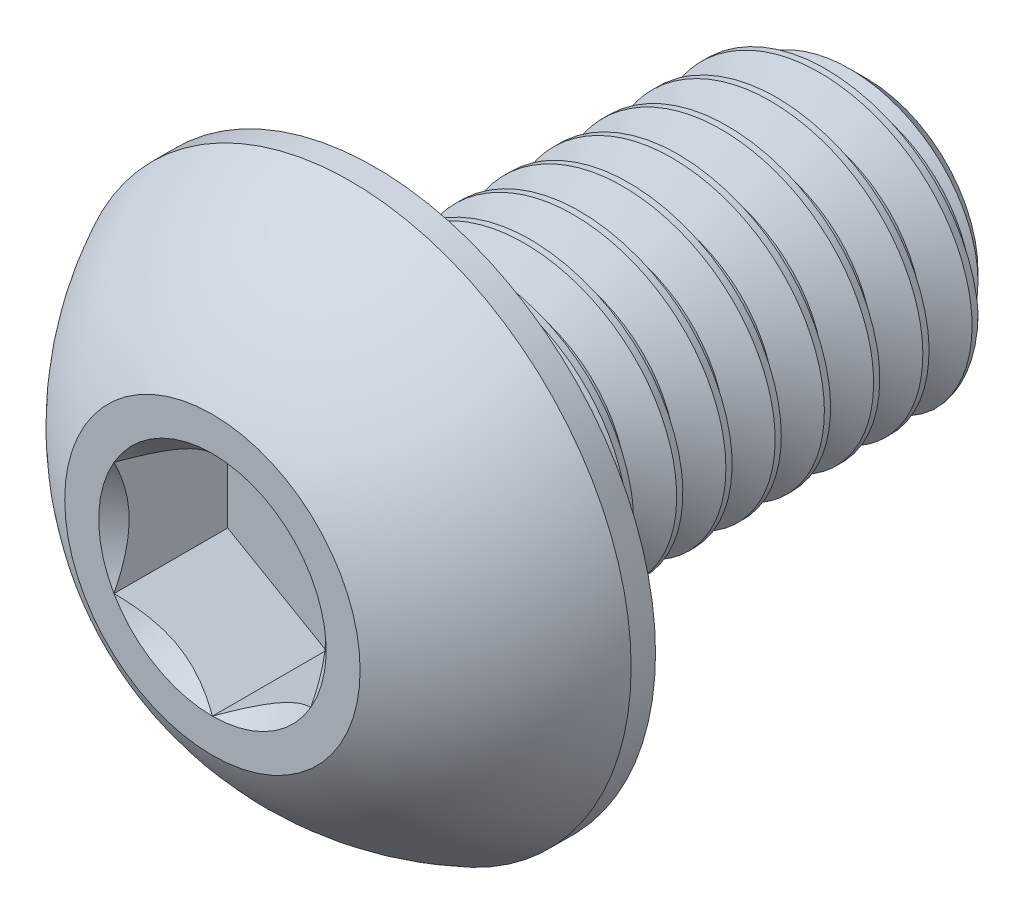
SolidWorks part; units mm, degrees
ref_plane "Front" through (0, 0, 0) normal (0, 0, 1) x (1, 0, 0)
ref_plane "Top" through (0, 0, 0) normal (0, 1, 0) x (1, 0, 0)
ref_plane "Right" through (0, 0, 0) normal (1, 0, 0) x (0, 0, -1)
sketch "Sketch1" plane through (0, 0, 0) normal (1, 0, 0) x (0, 0, -1)
  line L2 (1.65, 1.5) -> (6.65, 1.5)
  line L3 (6.65, 1.5) -> (6.65, 0)
  line L4 (6.65, 0) -> (1.65, 0)
  line L6 (1.4025, 2.85) -> (1.65, 2.85) construction
  line L7 (6.65, 1.5) -> (6.65, -1.5) construction
  line L8 (0, 0) -> (1.65, 0) construction
  line L9 (1.65, 2.85) -> (1.65, -2.85) construction
  line L11 (1.65, 1.5) -> (1.65, 0)
  line L13 (0, 1) -> (0, -1) construction
  line L14 (0, 1) -> (0, 1.5) construction
  line L15 (6.65, -1.5) -> (6.15, -1.5) construction
  arc A3 (0, 1.5) -> (1.4025, 2.85) centre (2.7948, 0) cw construction
  dimension "D1" = 0.2475
  dimension "Pitch" = 0.5
revolve "Revolve1" add sketch "Sketch1" angle 360 mid plane about L4
sketch "Sketch7" plane through (0, 0, 0) normal (1, 0, 0) x (0, 0, -1)
  line L6 (1.4025, 2.85) -> (1.65, 2.85) construction
  line L8 (0, 0) -> (1.65, 0) construction
  line L11 (1.65, 2.85) -> (1.65, -2.85) construction
  line L12 (1.4025, 2.85) -> (1.65, 2.85)
  line L13 (0, 0) -> (1.65, 0)
  line L14 (0, 1) -> (0, -1) construction
  line L15 (1.65, 2.85) -> (1.65, 0)
  line L16 (0, 1.5) -> (0, 0)
  arc A2 (1.4025, 2.85) -> (0, 1.5) centre (2.7948, 0) ccw construction
  arc A3 (1.4025, 2.85) -> (0, 1.5) centre (2.7948, 0) ccw
revolve "Revolve2" add sketch "Sketch7" angle 360 mid plane about L13
sketch "Sketch5" plane through (0, 0, 0) normal (0, 0, 1) x (1, 0, 0)
  line L1 (1, -0.5774) -> (1, 0.5774)
  line L2 (1, 0.5774) -> (0, 1.1547)
  line L3 (0, 1.1547) -> (-1, 0.5774)
  line L4 (-1, 0.5774) -> (-1, -0.5774)
  line L5 (-1, -0.5774) -> (0, -1.1547)
  line L6 (0, -1.1547) -> (1, -0.5774)
  circle A0 centre (0, 0) radius 1 construction
extrude "Cut-Extrude2" cut sketch "Sketch5" against normal blind 1.155
sketch "Sketch6" plane through (0, 0, 0) normal (0, 0, 1) x (1, 0, 0)
  circle A0 centre (0, 0) radius 1.1547
extrude "Cut-Extrude3" cut sketch "Sketch6" against normal blind 1.155 draft 45
sketch "Sketch11" plane through (0, 0, 0) normal (1, 0, 0) x (0, 0, -1)
  line L0 (1.65, -2.85) -> (1.65, 2.85)
  point P4 (1.65, 0)
split "Split1" trim tools "Sketch11" bodies to split 113 resulting bodies 119 120
sketch "Sketch10" plane through (0, 0, 0) normal (1, 0, 0) x (0, 0, -1)
  line L0 (6.65, 1.5) -> (6.65, -1.5) construction
  point P0 (5.9, -1.5)
  dimension "D1" = 0.75
sketch "Sketch3" plane through (0, 0, -6.65) normal (0, 0, -1) x (-1, 0, 0)
  circle A0 centre (0, 0) radius 1.5
curve "Helix/Spiral1" pitch 0.5 height 5.5 radius 1.5 centre (0, 0, -6.65) axis (0, 0, 1) start towards (0, 1, 0)
sketch "Sketch2" plane through (0, 0, 0) normal (1, 0, 0) x (0, 0, -1)
  line L0 (6.6187, 1.5541) -> (7.1187, 1.5541) construction
  line L1 (7.1187, 1.5541) -> (6.8687, 1.1211) construction
  line L2 (6.8687, 1.1211) -> (6.6187, 1.5541) construction
  line L3 (6.8687, 1.5541) -> (6.8687, 1.5) construction
  line L4 (6.8687, 1.5) -> (6.8687, 1.1752) construction
  line L5 (6.8687, 1.1752) -> (6.8687, 1.1211) construction
  line L6 (6.8375, 1.1752) -> (6.9, 1.1752)
  line L7 (6.65, 1.5) -> (7.0875, 1.5) construction
  line L8 (6.6344, 1.5271) -> (7.1031, 1.5271)
  line L9 (6.6344, 1.5271) -> (6.8375, 1.1752)
  line L10 (7.1031, 1.5271) -> (6.9, 1.1752)
  point P10 (6.8687, 1.1752)
  point P13 (6.8687, 1.5)
  point P16 (6.8687, 1.5271)
  dimension "D1" = 0.5
  dimension "D2" = 0.0625
chamfer "Chamfer1" distance 0.375 angle 45 1 edges at (0, 1.5, -6.65)
sweep "Cut-Sweep1" cut profiles "Sketch2" path "Helix/Spiral1" align with end faces yes
combine bodies "Combine1" operation type add bodies to combine 120 114
equation "\"D3@Helix/Spiral1\" = \"Lg@Sketch1\" + \"D4@Helix/Spiral1\""
equation "\"D1@Chamfer1\" = \"D4@Helix/Spiral1\" * .75"
equation "\"D1@Cut-Extrude2\" = \"Head Ht@Sketch1\" * .7"
equation "\"D1@Sketch1\" = \"Head Ht@Sketch1\" * .15"
equation "\"D1@Sketch10\" = \"D4@Helix/Spiral1\" * 1.5"
equation "\"D1@Cut-Extrude3\" = \"D1@Cut-Extrude2\""
equation "\"D4@Helix/Spiral1\"=\"Pitch@Sketch1\""
equation "\"D1@Sketch2\"=\"Pitch@Sketch1\""
equation "\"D2@Sketch2\"=\"D1@Sketch2\"/8"
